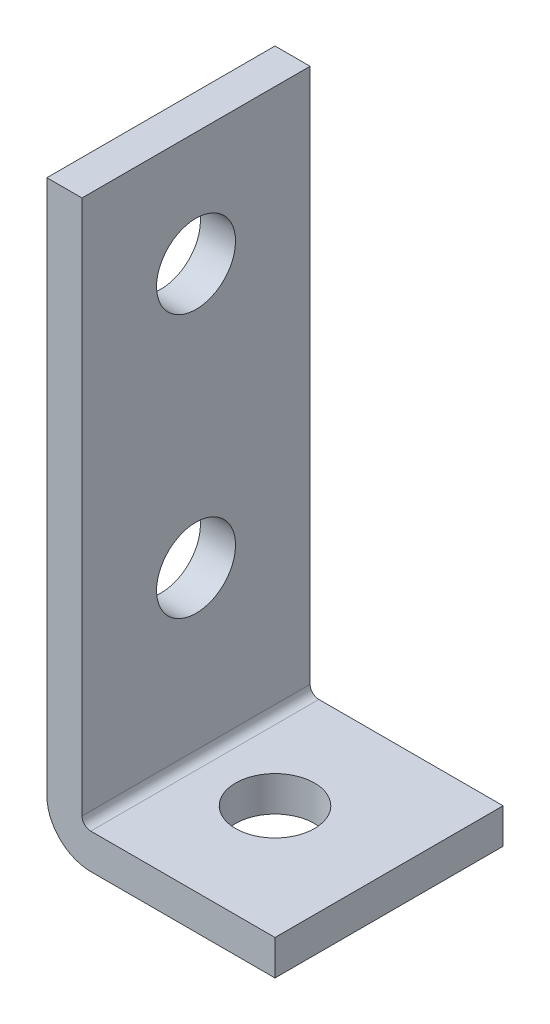
SolidWorks part; units mm, degrees
ref_plane "Front Plane" through (0, 0, 0) normal (0, 0, 1) x (1, 0, 0)
ref_plane "Top Plane" through (0, 0, 0) normal (0, 1, 0) x (1, 0, 0)
ref_plane "Right Plane" through (0, 0, 0) normal (1, 0, 0) x (0, 0, -1)
sketch "Sketch1" plane through (0, 0, 0) normal (0, 0, 1) x (1, 0, 0)
  line L0 (0, 104.775) -> (0, 7.9375)
  line L1 (7.9375, 0) -> (41.275, 0)
  arc A0 (0, 7.9375) -> (7.9375, 0) centre (7.9375, 7.9375) ccw
  dimension "D1" = 7.9375
  dimension "B" = 41.275
  dimension "A" = 104.775
extrude "Extrude-Thin1" add sketch "Sketch1" along normal mid plane 41.275 thin thin type one direction reverse wall 6.35
sketch "Sketch2" plane through (0, 6.35, 0) normal (0, 1, 0) x (1, 0, 0)
  line L0 (41.275, -20.6375) -> (41.275, 20.6375) construction
  circle A0 centre (20.6375, 0) radius 7.1438
  dimension "Hole Size" = 14.2875
  dimension "edge" = 20.6375
extrude "Cut-Extrude1" cut sketch "Sketch2" against normal through all
sketch "Sketch3" plane through (6.35, 0, 0) normal (1, 0, 0) x (0, 0, -1)
  line L0 (-20.6375, 104.775) -> (20.6375, 104.775) construction
  circle A0 centre (0, 84.1375) radius 7.1438
  circle A1 centre (0, 36.5125) radius 7.1438
  dimension "D1" = 20.6375
  dimension "D2" = 14.2875
  dimension "Hole Spacing" = 47.625
extrude "Cut-Extrude2" cut sketch "Sketch3" against normal through all
equation "\"D2@Sketch3\" = \"Hole Size@Sketch2\""
